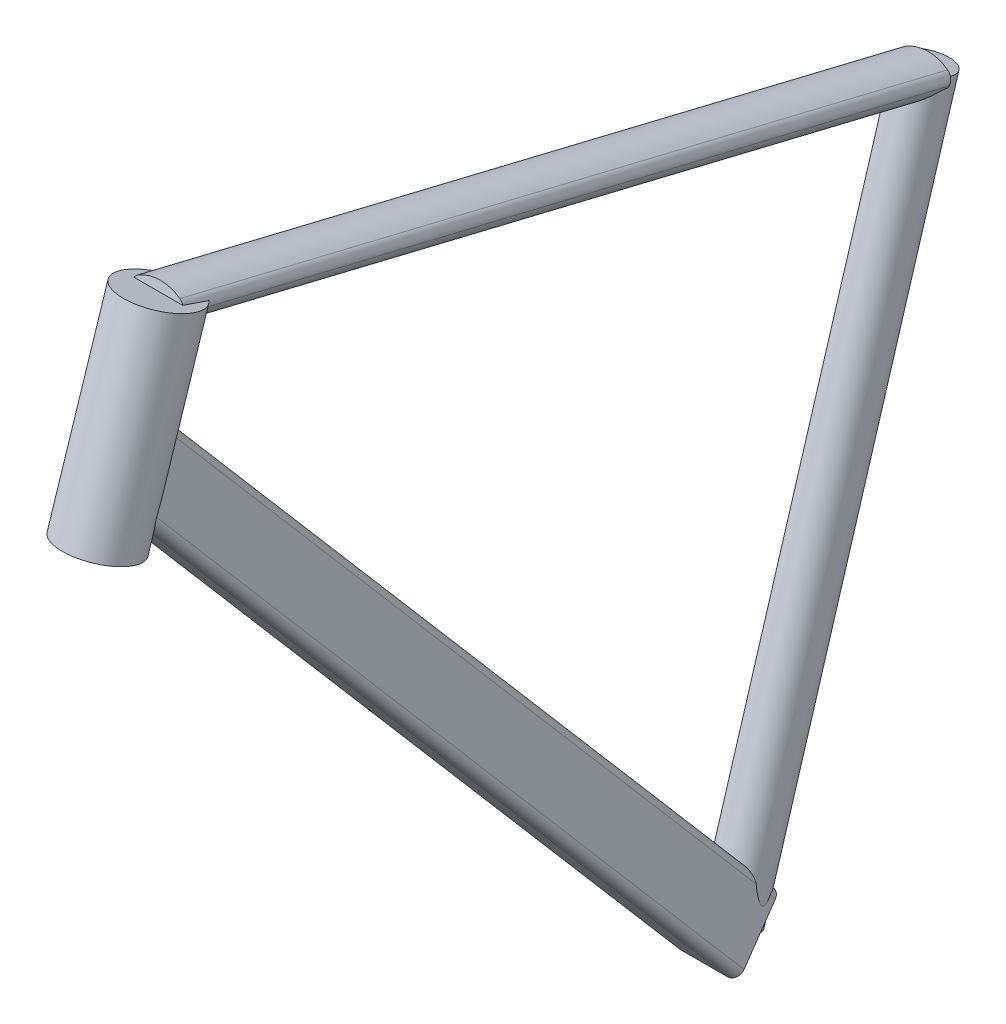
SolidWorks part; units mm, degrees
ref_plane "Plan de face" through (0, 0, 0) normal (0, 0, 1) x (1, 0, 0)
ref_plane "Plan de dessus" through (0, 0, 0) normal (0, 1, 0) x (1, 0, 0)
ref_plane "Plan de droite" through (0, 0, 0) normal (1, 0, 0) x (0, 0, -1)
sketch "Esquisse1" plane through (0, 0, 0) normal (1, 0, 0) x (0, 0, -1)
  line L0 (0, 0) -> (-416.4955, 485.9336)
  line L4 (-416.4955, 485.9336) -> (-390.3242, 566.9614)
  line L5 (-390.3242, 566.9614) -> (132.9546, 440.367)
  line L6 (132.9546, 440.367) -> (0, 0)
  line L7 (-390.3242, 566.9614) -> (220.5054, 566.9614) construction
  line L8 (0, 0) -> (154.0318, 132.0212) construction
  line L9 (-416.4955, 485.9336) -> (-477.5022, 505.6383) construction
  line L10 (0, 0) -> (73.466, -22.1807) construction
  line L11 (-390.3242, 566.9614) -> (-377.98, 617.9864) construction
  dimension "D1" = 13.6
  dimension "D2" = 35.8
  dimension "D3" = 640
  dimension "D4" = 86.8
  dimension "D5" = 94.3
  dimension "D6" = 460
ref_plane "Plan1" through (0, 0, 0) normal (0, 0.7593, 0.6508) x (1, 0, 0)
sketch "Esquisse2" plane through (0, 0, 0) normal (0, 0.7593, 0.6508) x (1, 0, 0)
  line L0 (15, 20.051) -> (21.8, -17.0688)
  line L1 (15.8982, -24.15) -> (-15.8982, -24.15)
  line L2 (-21.8, -17.0688) -> (-15, 20.051)
  line L3 (-10.0818, 24.15) -> (10.0818, 24.15)
  line L4 (0, 0) -> (0, 202.8679) construction
  line L5 (0, 24.15) -> (0, -24.15) construction
  arc A0 (21.8, -17.0688) -> (15.8982, -24.15) centre (15.8982, -18.15) cw
  arc A1 (-15.8982, -24.15) -> (-21.8, -17.0688) centre (-15.8982, -18.15) cw
  arc A2 (15, 20.051) -> (10.0818, 24.15) centre (10.0818, 19.15) ccw
  arc A3 (-15, 20.051) -> (-10.0818, 24.15) centre (-10.0818, 19.15) cw
  point P2 (0, 24.15)
  point P9 (0, -24.15)
  point P21 (0, 0)
  dimension "D2" = 6
  dimension "D4" = 5
  dimension "D1" = 48.3
  dimension "D3" = 43.6
  dimension "D5" = 30
extrude "Boss.-Extru.1" add sketch "Esquisse2" along direction (0, 0.7593, 0.6508) on the side of the normal up to vertex (640 mm away) up to point (0, 485.9336, 416.4955)
ref_plane "Plan2" through (0, 318.2123, -102.7798) normal (0, 0.9516, -0.3074) x (1, 0, 0)
sketch "Esquisse3" plane through (0, 318.2123, -102.7798) normal (0, 0.9516, -0.3074) x (1, 0, 0)
  circle A0 centre (0, -545.6897) radius 25
  dimension "D1" = 50
extrude "Boss.-Extru.2" add sketch "Esquisse3" along normal up to vertex (85.1495 mm away) and the other way blind 50 up to point (0, 566.9614, 390.3242)
ref_plane "Plan3" through (0, 0, 0) normal (0, -0.9573, 0.289) x (-1, 0, 0)
sketch "Esquisse4" plane through (0, 0, 0) normal (0, -0.9573, 0.289) x (-1, 0, 0)
  circle A0 centre (0, 0) radius 16.25
  dimension "D1" = 32.5
extrude "Boss.-Extru.3" add sketch "Esquisse4" against normal up to vertex (460 mm away) up to point (0, 440.367, -132.9546)
sketch "Esquisse5" plane through (0, 15.7162, -18.3364) normal (0, 0.6508, -0.7593) x (-1, 0, 0)
  circle A0 centre (0, 284.7335) radius 2
  circle A1 centre (0, 219.7335) radius 2
  ellipse E0 centre (0, 15.4446) end of major axis (0, -3.8444) minor radius 16.25 (10.0818, 30.5723) -> (-10.0818, 30.5723) ccw construction
  point P11 (0, 34.7335)
  dimension "D3" = 4
  dimension "D1" = 65
  dimension "D2" = 185
ref_plane "Plan4" through (0, 120.5565, 498.3209) normal (0, -0.2351, -0.972) x (-1, 0, 0)
sketch "Esquisse6" plane through (0, 120.5565, 498.3209) normal (0, -0.2351, -0.972) x (-1, 0, 0)
  line L0 (0, 459.2828) -> (0, 511.7797) construction
  line L1 (0, 374.3729) -> (0, 459.2828) construction
  line L2 (-18, 459.2828) -> (18, 459.2828) construction
  arc A0 (-18, 459.2828) -> (18, 459.2828) centre (0, 435.2828) cw
  arc A1 (-18, 459.2828) -> (18, 459.2828) centre (0, 460.863) ccw
  dimension "D1" = 30
  dimension "D2" = 36
extrude "Boss.-Extru.4" add sketch "Esquisse6" along normal up to vertex (538.3743 mm away) up to point (0, 440.367, -132.9546)
fillet "Congé2" radius 6 2 edges at (-18, 503.6642, 128.6848) (18, 503.6642, 128.6848)
